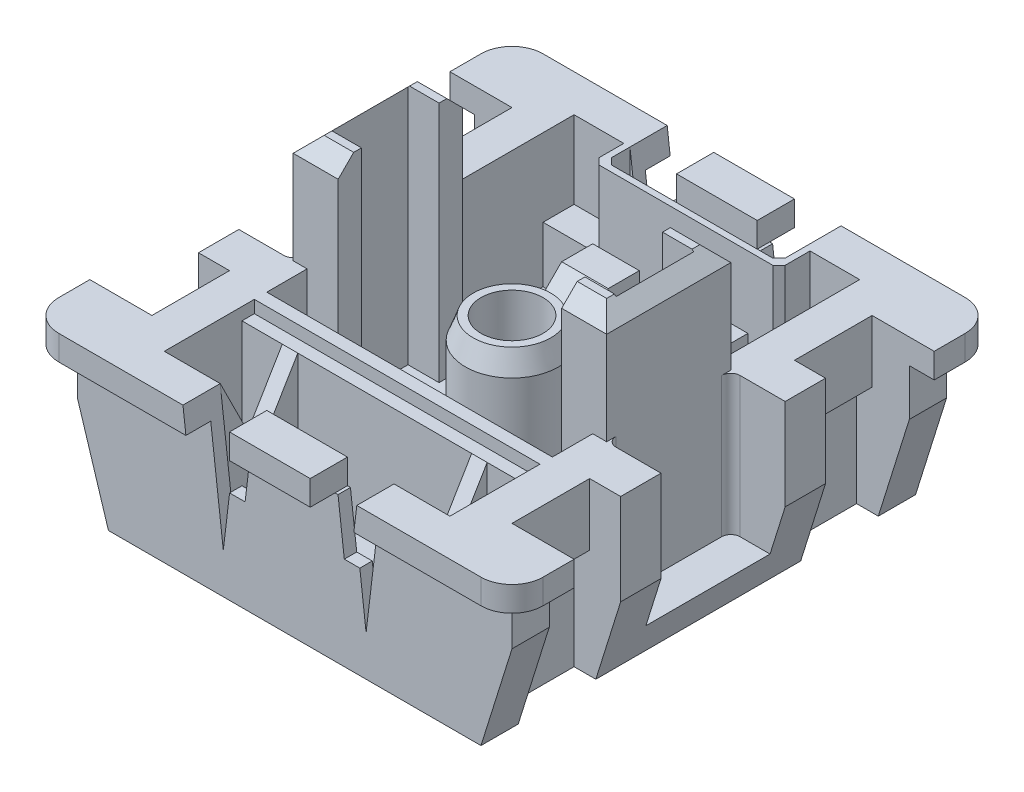
SolidWorks part; units mm, degrees
ref_plane "Front Plane" through (0, 0, 0) normal (0, 0, 1) x (1, 0, 0)
ref_plane "Top Plane" through (0, 0, 0) normal (0, 1, 0) x (1, 0, 0)
ref_plane "Right Plane" through (0, 0, 0) normal (1, 0, 0) x (0, 0, -1)
sketch "Sketch2" plane through (0, 0, 0) normal (0, 1, 0) x (1, 0, 0)
  line L1 (-7.8, 7.8) -> (7.8, 7.8)
  line L2 (-7.8, 7.8) -> (-7.8, -7.8)
  line L3 (-7.8, -7.8) -> (7.8, -7.8)
  line L4 (7.8, 7.8) -> (7.8, -7.8)
  line L5 (-7.8, 7.8) -> (7.8, -7.8) construction
  line L6 (-7.8, -7.8) -> (7.8, 7.8) construction
  point P0 (0, 0)
  dimension "D1" = 15.6
  dimension "D2" = 15.6
extrude "Boss-Extrude1" add sketch "Sketch2" along normal blind 5.5
sketch "Sketch3" plane through (0, 0, 0) normal (0, -1, 0) x (1, 0, 0)
  line L1 (-7.8, 7.8) -> (7.8, 7.8)
  line L2 (-7.8, 7.8) -> (-7.8, -7.8)
  line L3 (-7.8, -7.8) -> (7.8, -7.8)
  line L4 (7.8, 7.8) -> (7.8, -7.8)
  line L5 (-7.8, 7.8) -> (7.8, -7.8) construction
  line L6 (-7.8, -7.8) -> (7.8, 7.8) construction
  line L7 (-7, 7) -> (7, 7)
  line L8 (-7, 7) -> (-7, -7)
  line L9 (-7, -7) -> (7, -7)
  line L10 (7, 7) -> (7, -7)
  line L11 (-7, 7) -> (7, -7) construction
  line L12 (-7, -7) -> (7, 7) construction
  point P0 (0, 0)
  point P7 (0, 0)
  dimension "D1" = 14
extrude "Cut-Extrude1" cut sketch "Sketch3" against normal blind 4.7
sketch "Sketch4" plane through (0, 0, -7) normal (0, 0, -1) x (-1, 0, 0)
  line L0 (-7, 0) -> (-6, 0)
  line L1 (7, 0) -> (-7, 0) construction
  line L2 (-7, 0) -> (-7, 3.2)
  line L3 (-7, 4.7) -> (-7, 0) construction
  line L4 (-7, 3.2) -> (-6, 0)
  line L5 (7, 0) -> (7, 3.2)
  line L6 (7, 4.7) -> (7, 0) construction
  line L7 (7, 0) -> (6, 0)
  line L8 (6, 0) -> (7, 3.2)
  dimension "D1" = 3.2
  dimension "D2" = 1
  dimension "D3" = 1
extrude "Cut-Extrude2" cut sketch "Sketch4" against normal through all
sketch "Sketch5" plane through (0, 5.5, 0) normal (0, 1, 0) x (1, 0, 0)
  line L8 (-7.8, 7.8) -> (-7.8, -7.8) construction
  line L9 (-5.8, 5.8) -> (-7.8, 5.8)
  line L10 (-5.8, 5.8) -> (-5.8, 3.3)
  line L11 (-5.8, 3.3) -> (-7.8, 3.3)
  line L12 (5.8, -5.8) -> (5.8, 5.8)
  line L13 (5.8, 5.8) -> (-5.8, 5.8)
  line L14 (-5.8, 5.8) -> (-5.8, -5.8)
  line L15 (-5.8, -5.8) -> (5.8, -5.8)
  line L16 (5.8, -5.8) -> (5.8, 5.8)
  line L17 (5.8, 5.8) -> (-5.8, 5.8)
  line L18 (-5.8, 5.8) -> (-5.8, -5.8)
  line L19 (-5.8, -5.8) -> (5.8, -5.8)
  line L20 (-7.8, 5.8) -> (-7.8, 3.3)
  line L21 (7.8, -7.8) -> (7.8, 7.8) construction
  line L22 (-5.8, -5.8) -> (-7.8, -5.8)
  line L23 (-5.8, -5.8) -> (-5.8, -3.3)
  line L24 (-5.8, -3.3) -> (-7.8, -3.3)
  line L25 (-7.8, -5.8) -> (-7.8, -3.3)
  line L26 (5.8, 5.8) -> (7.8, 5.8)
  line L27 (5.8, 5.8) -> (5.8, 3.3)
  line L28 (5.8, 3.3) -> (7.8, 3.3)
  line L29 (7.8, 5.8) -> (7.8, 3.3)
  line L30 (-6.8, 3.3) -> (-6.8, -3.3)
  line L31 (5.8, -5.8) -> (7.8, -5.8)
  line L32 (5.8, -5.8) -> (5.8, -3.3)
  line L33 (5.8, -3.3) -> (7.8, -3.3)
  line L34 (7.8, -5.8) -> (7.8, -3.3)
  line L35 (6.8, 3.3) -> (6.8, -3.3)
  line L36 (-7.8, 3.3) -> (-7.8, -3.3)
  line L37 (7.8, 3.3) -> (7.8, -3.3)
  line M7 (7.8, -7.8) -> (7.8, 7.8)
  line M9 (-7.8, 7.8) -> (-7.8, -7.8)
  dimension "D2" = 2.5
  dimension "D3" = 2.5
  dimension "D1" = 2
extrude "Cut-Extrude3" cut sketch "Sketch5" against normal through all contours L11 L10 L9 M9 | L16 L28 L26 M7 | L18 L24 L22 M9 | L33 L16 L31 M7 | L30 L11 L24 M9 | L28 L35 L33 M7 region at (-6.8, 5.5, -4.55) region at (6.8, 5.5, -4.55) region at (-7.3, 5.5, 0) region at (-6.8, 5.5, 4.55) region at (6.8, 5.5, 4.55) region at (7.3, 5.5, 0)
sketch "Sketch6" plane through (0, 5.5, 0) normal (0, 1, 0) x (1, 0, 0)
  line L0 (-6.8, 3.3) -> (-6.8, -3.3) construction
  line L1 (-6.8, 2) -> (-5.05, 2)
  line L2 (-6.8, 2) -> (-6.8, -2)
  line L3 (-6.8, -2) -> (-5.05, -2)
  line L4 (-5.05, 2) -> (-5.05, -2)
  line L5 (-5.8, -3.3) -> (-6.8, -3.3) construction
  line L6 (6.8, 3.3) -> (6.8, -3.3) construction
  line L7 (6.8, 2) -> (5.05, 2)
  line L8 (6.8, 2) -> (6.8, -2)
  line L9 (6.8, -2) -> (5.05, -2)
  line L10 (5.05, 2) -> (5.05, -2)
  dimension "D1" = 1.75
  dimension "D2" = 1.3
  dimension "D3" = 1.3
  dimension "D4" = 1.75
  dimension "D5" = 4
extrude "Cut-Extrude4" cut sketch "Sketch6" against normal blind 4.5
sketch "Sketch7" plane through (0, 5.5, 0) normal (0, 1, 0) x (1, 0, 0)
  line L0 (7.8, 7.8) -> (-7.8, 7.8) construction
  line L1 (-5.8, 7.8) -> (-4.6, 7.8)
  line L2 (-5.8, 7.8) -> (-5.8, 6.6)
  line L3 (-5.8, 6.6) -> (-4.6, 6.6)
  line L4 (-4.6, 7.8) -> (-4.6, 6.6)
  line L5 (-7.8, -7.8) -> (7.8, -7.8) construction
  line L6 (5.8, -7.8) -> (4.6, -7.8)
  line L7 (5.8, -7.8) -> (5.8, -6.6)
  line L8 (5.8, -6.6) -> (4.6, -6.6)
  line L9 (4.6, -7.8) -> (4.6, -6.6)
  line L11 (-4.6, 6.6) -> (4.6, 6.6)
  line L12 (-4.6, 6.6) -> (-4.6, -6.6)
  line L13 (-4.6, -6.6) -> (4.6, -6.6)
  line L14 (4.6, 6.6) -> (4.6, -6.6)
  dimension "D1" = 1.2
  dimension "D2" = 1.2
  dimension "D3" = 2
  dimension "D4" = 2
  dimension "D5" = 1.2
  dimension "D6" = 1.2
extrude "Cut-Extrude5" cut sketch "Sketch7" against normal blind 4.3 contours L14 L11 L12 L13 region at (0, 5.5, 0)
sketch "Sketch8" plane through (0, 1.2, 0) normal (0, 1, 0) x (1, 0, 0)
  line L0 (4.6, 6.6) -> (4.6, -6.6) construction
  line L1 (4.6, -4.1) -> (-4.6, -4.1)
  line L2 (4.6, -4.1) -> (4.6, -3.3)
  line L3 (4.6, -3.3) -> (-4.6, -3.3)
  line L4 (-4.6, -4.1) -> (-4.6, -3.3)
  line L5 (-4.6, 6.6) -> (-4.6, -6.6) construction
  line L6 (-4.6, -6.6) -> (4.6, -6.6) construction
  dimension "D1" = 0.8
  dimension "D2" = 2.5
extrude "Boss-Extrude2" add sketch "Sketch8" along normal blind 4.3
sketch "Sketch9" plane through (0, 5.5, 0) normal (0, 1, 0) x (1, 0, 0)
  line L1 (4.6, -4.1) -> (-4.6, -4.1)
  line L2 (4.6, -4.1) -> (4.6, -3.7)
  line L3 (4.6, -3.7) -> (-4.6, -3.7)
  line L4 (-4.6, -4.1) -> (-4.6, -3.7)
  dimension "D1" = 0.4
extrude "Cut-Extrude6" cut sketch "Sketch9" against normal blind 0.4
sketch "Sketch10" plane through (0, 0, 7.8) normal (0, 0, 1) x (1, 0, 0)
  line L0 (7.8, 4.7) -> (-7.8, 4.7) construction
  line L1 (-7.8, 5.5) -> (-2.8, 5.5)
  line L2 (-7.8, 5.5) -> (-7.8, 4.7)
  line L3 (-7.8, 4.7) -> (-2.8, 4.7)
  line L4 (-2.8, 5.5) -> (-2.8, 4.7)
  line L5 (7, 4.7) -> (-7, 4.7) construction
  line L6 (7.8, 5.5) -> (2.8, 5.5)
  line L7 (7.8, 5.5) -> (7.8, 4.7)
  line L8 (7.8, 4.7) -> (2.8, 4.7)
  line L9 (2.8, 5.5) -> (2.8, 4.7)
  line L10 (-2.8, 5.5) -> (-1.3, 5.5)
  line L11 (-2.8, 5.5) -> (-2.8, 4.7)
  line L12 (-2.8, 4.7) -> (-1.3, 4.7)
  line L13 (-1.3, 5.5) -> (-1.3, 4.7)
  line L14 (-2.8, 1.3) -> (-2.3, 1.3)
  line L15 (2.8, 5.5) -> (1.3, 5.5)
  line L16 (2.8, 5.5) -> (2.8, 4.7)
  line L17 (2.8, 4.7) -> (1.3, 4.7)
  line L18 (1.3, 5.5) -> (1.3, 4.7)
  line L19 (-2.8, 4.7) -> (2.8, 4.7)
  line L20 (-2.8, 4.7) -> (-2.8, 1.3)
  line L21 (-2.8, 1.3) -> (2.8, 1.3)
  line L22 (2.8, 4.7) -> (2.8, 1.3)
  line L23 (2.8, 1.3) -> (2.3, 1.3)
  line L24 (-2.8, 5.5) -> (-2.3, 1.3)
  line L25 (2.8, 5.5) -> (2.3, 1.3)
  line L26 (-2.8, 5.5) -> (-1.8, 5.5)
  line L27 (2.8, 5.5) -> (1.8, 5.5)
  line L28 (6, 0) -> (-6, 0) construction
  line L29 (-2.8, 0) -> (2.8, 0)
  line L30 (-2.8, 0) -> (-2.8, 3)
  line L31 (-2.8, 3) -> (2.8, 3)
  line L32 (2.8, 0) -> (2.8, 3)
  line L33 (-2.3, 1.3) -> (-1.8, 1.3)
  line L34 (-2.3, 1.3) -> (-2.0976, 3)
  line L35 (2.3, 1.3) -> (2.0976, 3)
  line L36 (2.3, 1.3) -> (1.8, 1.3)
  line L37 (1.8, 1.3) -> (1.3, 5.5)
  line L38 (1.3, 5.5) -> (1.5976, 3)
  line L39 (1.5976, 3) -> (2.0976, 3)
  line L40 (-1.3, 5.5) -> (-1.8, 1.3)
  line L41 (-1.3, 5.5) -> (-1.5976, 3)
  line L42 (-1.5976, 3) -> (-2.0976, 3)
  line M23 (-7.8, 4.7) -> (7.8, 4.7)
  line M25 (7.8, 5.5) -> (-7.8, 5.5)
  dimension "D1" = 5
  dimension "D2" = 5
  dimension "D3" = 1.5
  dimension "D4" = 1.5
  dimension "D5" = 3.4
  dimension "D6" = 0.5
  dimension "D7" = 0.5
  dimension "D8" = 1
  dimension "D9" = 1
extrude "Cut-Extrude7" cut sketch "Sketch10" against normal blind 1.2 contours L40 L10 L24 L19 M25 | L13 L40 M23 | L40 L19 L24 L31 | L24 L34 L31 | L35 L25 L31 | L37 L31 L25 L19 | L37 L19 L25 L15 M25 | L37 L18 M23 region at (-2.05, 5.109, 7.8) region at (-2.05, 3.9018, 7.8) region at (-1.3317, 4.9667, 7.8) region at (-2.3, 2.4333, 7.8) region at (1.3317, 4.9667, 7.8) region at (2.05, 5.109, 7.8) region at (2.05, 3.9018, 7.8) region at (2.3, 2.4333, 7.8)
sketch "Sketch11" plane through (0, 1.2, 0) normal (0, 1, 0) x (1, 0, 0)
  line L0 (-4.6, -4.1) -> (4.6, -4.1) construction
  line L1 (-2.8, -6.6) -> (-3.3, -6.6)
  line L2 (-2.8, -6.6) -> (-2.8, -4.1)
  line L3 (-2.8, -4.1) -> (-3.3, -4.1)
  line L4 (-3.3, -6.6) -> (-3.3, -4.1)
  line L5 (-4.6, -4.1) -> (4.6, -4.1) construction
  line L6 (2.8, -6.6) -> (3.3, -6.6)
  line L7 (2.8, -6.6) -> (2.8, -4.1)
  line L8 (2.8, -4.1) -> (3.3, -4.1)
  line L9 (3.3, -6.6) -> (3.3, -4.1)
  dimension "D1" = 0.5
  dimension "D2" = 0.5
extrude "Boss-Extrude3" add sketch "Sketch11" along normal blind 4.3
sketch "Sketch12" plane through (3.3, 0, 0) normal (1, 0, 0) x (0, 0, -1)
  line L0 (-4.1, 5.1) -> (-5.35, 3)
  line L3 (-5.35, 3) -> (-6.6, 5.5)
  line L4 (-6.6, 5.5) -> (-4.1, 5.5)
  line L5 (-4.1, 5.5) -> (-4.1, 5.1)
extrude "Cut-Extrude8" cut sketch "Sketch12" against normal blind 6.6
fillet "Fillet2" radius 0.3 4 edges at (-5.05, 3.25, -2) (-5.05, 3.25, 2) (5.05, 3.25, -2) (5.05, 3.25, 2)
fillet "Fillet3" radius 1 4 edges at (7.8, 5.1, -7.8) (7.8, 5.1, 7.8) (-7.8, 5.1, -7.8) (-7.8, 5.1, 7.8)
sketch "Sketch13" plane through (0, 1.2, 0) normal (0, 1, 0) x (1, 0, 0)
  line L0 (0, 0) -> (4.6, 0)
  line L1 (4.6, 6.6) -> (4.6, -3.3) construction
  line L2 (4.6, 0) -> (4.6, -1.25)
  line L3 (4.6, -1.25) -> (3.6, -1.25)
  line L4 (3.6, -1.25) -> (3.6, -2)
  line L5 (3.6, -2) -> (4.6, -2)
  line L6 (4.6, -2) -> (4.6, -1.25)
  line L7 (4.6, 0) -> (4.6, 2)
  line L8 (4.6, 6.6) -> (4.6, -3.3) construction
  line L9 (-4.6, 6.6) -> (-4.6, -3.3) construction
  line L10 (4.6, 2) -> (3.6, 2)
  line L11 (4.6, 2) -> (4.6, 1.25)
  line L12 (4.6, 1.25) -> (3.6, 1.25)
  line L13 (3.6, 2) -> (3.6, 1.25)
  line L14 (-4.6, -2) -> (-3.6, -2)
  line L15 (-4.6, -2) -> (-4.6, -1.25)
  line L16 (-4.6, -1.25) -> (-3.6, -1.25)
  line L17 (-3.6, -2) -> (-3.6, -1.25)
  line L18 (-4.6, 6.6) -> (-4.6, -3.3) construction
  line L19 (-4.6, 2) -> (-3.6, 2)
  line L20 (-4.6, 2) -> (-4.6, 1.25)
  line L21 (-4.6, 1.25) -> (-3.6, 1.25)
  line L22 (-3.6, 2) -> (-3.6, 1.25)
  circle A0 centre (0, 0) radius 1
  circle A1 centre (0, 0) radius 1.5
  line M10 (-4.6, 6.6) -> (-4.6, -3.3)
  dimension "D8" = 2
  dimension "D9" = 3
  dimension "D1" = 1.25
  dimension "D2" = 1
  dimension "D3" = 0.75
  dimension "D4" = 2
  dimension "D5" = 0.75
  dimension "D6" = 1
  dimension "D7" = 1
extrude "Boss-Extrude4" add sketch "Sketch13" along normal blind 4.3 contours A1 A0 | L10 L13 L12 L7 | L22 L19 L21 M10 | L14 L17 L16 M10 | L3 L4 L5 L6 region at (-1.4576, 1.2, 0) region at (4.1, 1.2, -1.625) region at (-4.1, 1.2, 1.625) region at (-4.1, 1.2, -1.625)
sketch "Sketch14" plane through (0, 5.5, 0) normal (0, 1, 0) x (1, 0, 0)
  line L0 (-3.6, 2) -> (-5.05, 2)
  line L1 (-5.05, 2) -> (-5.05, -2)
  line L2 (-5.05, -2) -> (-3.6, -2)
  line L3 (-3.6, -2) -> (-3.6, -1.25)
  line L4 (-3.6, -1.25) -> (-4.6, -1.25)
  line L5 (-4.6, -1.25) -> (-4.6, 1.25)
  line L6 (-4.6, 1.25) -> (-3.6, 1.25)
  line L7 (-3.6, 1.25) -> (-3.6, 2)
  line L8 (-5.05, 2) -> (-3.6, 2)
  line L9 (3.6, 2) -> (5.05, 2)
  line L10 (5.05, 2) -> (5.05, -2)
  line L11 (5.05, -2) -> (3.6, -2)
  line L12 (3.6, -2) -> (3.6, -1.25)
  line L13 (3.6, -1.25) -> (4.6, -1.25)
  line L14 (4.6, -1.25) -> (4.6, 1.25)
  line L15 (4.6, 1.25) -> (3.6, 1.25)
  line L16 (3.6, 1.25) -> (3.6, 2)
extrude "Boss-Extrude5" add sketch "Sketch14" along normal blind 3.5 contours L6 L7 L0 L1 L2 L3 L4 L5 | L16 L15 L14 L13 L12 L11 L10 L9 region at (-3.6425, 5.5, -1.625) region at (4.325, 5.5, -1.9575)
chamfer "Chamfer3" distance 0.5 angle 45 6 edges at (4.325, 9, 2) (5.05, 9, 0) (4.325, 9, -2) (-4.325, 9, 2) (-4.325, 9, -2) (-5.05, 9, 0)
chamfer "Chamfer4" distance 0.25 angle 70 1 edges at (0, 5.5, 1.5) first distance on face at (0, 5.5, 1.5)
sketch "Sketch16" plane through (0, 1.2, 0) normal (0, 1, 0) x (1, 0, 0)
  line L0 (-3.6, 2) -> (-3.6, 1.25) construction
  line L2 (-2.5, 1.6) -> (-2.5, 5.1)
  line L4 (-2.5, 1.6) -> (-2.5, 5.1)
  line L5 (-2.5, 5.1) -> (2.5, 5.1)
  line L6 (2.5, 5.1) -> (2.5, 1.6)
  line L7 (2.5, 1.6) -> (1.9209, 1.6)
  line L8 (-1.9209, 1.6) -> (-2.5, 1.6)
  line L9 (-4.6, 6.6) -> (4.6, 6.6) construction
  line L10 (2.5, 5.1) -> (-2.5, 5.1)
  arc A0 (1.9209, 1.6) -> (-1.9209, 1.6) centre (0, 0) ccw
  dimension "D5" = 2.5
  dimension "D1" = 3.5
  dimension "D2" = 0
  dimension "D3" = 1.1
  dimension "D4" = 5
  dimension "D6" = 1.5
extrude "Boss-Extrude6" add sketch "Sketch16" along normal blind 2.5 contours A0 L7 L6 L5 L2 L8 region at (0, 1.2, -3.5703)
sketch "Sketch17" plane through (2.5, 0, 0) normal (1, 0, 0) x (0, 0, -1)
  line L1 (5.1, 3.7) -> (1.6, 3.7) construction
  line L2 (1.6, 3.7) -> (1.6, 3.2)
  line L3 (1.6, 3.7) -> (1.6, 1.2) construction
  line L4 (1.6, 3.2) -> (3.6, 3.2)
  line L5 (1.6, 3.7) -> (4.1, 3.7)
  line L6 (4.1, 3.7) -> (3.6, 3.2)
  dimension "D2" = 0.5
  dimension "D3" = 2
extrude "Cut-Extrude9" cut sketch "Sketch17" against normal blind 5
sketch "Sketch18" plane through (-2.5, 0, 0) normal (-1, 0, 0) x (0, 0, 1)
  line L0 (-3.6, 3.2) -> (-3.1, 3.2)
  line L1 (-1.6, 3.2) -> (-3.6, 3.2) construction
  line L2 (-3.1, 3.2) -> (-3.1, 2.7)
  line L3 (-3.6, 3.2) -> (-3.1, 2.7)
  dimension "D1" = 0.5
  dimension "D2" = 0.5
extrude "Cut-Extrude10" cut sketch "Sketch18" against normal blind 4.5
sketch "Sketch19" plane through (0, 3.2, 0) normal (0, 1, 0) x (1, 0, 0)
  line L1 (-2.5, 3.1) -> (2, 3.1)
  line L2 (-2.5, 3.1) -> (-2.5, 2.5)
  line L3 (-2.5, 2.5) -> (2, 2.5)
  line L4 (2, 3.1) -> (2, 2.5)
  line L5 (0, 2.5) -> (1, 2.5)
  line L6 (0, 2.5) -> (0, 2.2913)
  line L7 (0, 2.2913) -> (1, 2.2913)
  line L8 (1, 2.5) -> (1, 2.2913)
  line L9 (0, 2.5) -> (-1, 2.5)
  line L10 (0, 2.5) -> (0, 2.2913)
  line L11 (0, 2.2913) -> (-1, 2.2913)
  line L12 (-1, 2.5) -> (-1, 2.2913)
  arc A0 (1.9209, 1.6) -> (-1.9209, 1.6) centre (0, 0) ccw construction
  arc A1 (1.9209, 1.6) -> (-1.9209, 1.6) centre (0, 0) ccw construction
  line M2 (2, 3.1) -> (-2.5, 3.1)
  line M3 (-2.5, 3.1) -> (-2.5, 1.6)
  arc M5 (-1.9209, 1.6) -> (1.9209, 1.6) centre (0, 0) cw
  dimension "D1" = 1
  dimension "D2" = 1
  dimension "D3" = 0.6
extrude "Cut-Extrude15" cut sketch "Sketch19" against normal blind 2 contours L3 L12 M5 | L8 L3 M5 | L4 L3 M2 M3 region at (-0.25, 3.2, -2.8) region at (-0.7521, 3.2, -2.4379) region at (0.7521, 3.2, -2.4379)
sketch "Sketch20" plane through (0, 3.7, 0) normal (0, 1, 0) x (1, 0, 0)
  line L0 (-2.5, 5.1) -> (2.5, 5.1) construction
  line L1 (-1, 5.1) -> (1, 5.1)
  line L2 (-1, 5.1) -> (-1, 3.1)
  line L3 (-1, 3.1) -> (1, 3.1)
  line L4 (1, 5.1) -> (1, 3.1)
  line L5 (2, 3.1) -> (-2.5, 3.1) construction
  line L6 (-2.5, 4.1) -> (-2.5, 5.1) construction
  line L8 (2.5, 5.1) -> (2.5, 4.1) construction
  dimension "D1" = 1.5
  dimension "D2" = 1.5
extrude "Cut-Extrude16" cut sketch "Sketch20" against normal blind 1
chamfer "Chamfer5" distance 0.5 1 edges at (0, 2.7, -3.1)
sketch "Sketch21" plane through (0, 1.2, 0) normal (0, 1, 0) x (1, 0, 0)
  line L0 (4.6, 6.6) -> (4.6, 2) construction
  line L1 (-4.6, 6.6) -> (4.6, 6.6)
  line L2 (-4.6, 6.6) -> (-4.6, 5.6)
  line L3 (-4.6, 5.6) -> (4.6, 5.6)
  line L4 (4.6, 6.6) -> (4.6, 5.6)
  dimension "D1" = 1
extrude "Boss-Extrude7" add sketch "Sketch21" along normal up to surface (4.3 mm away) up to face at (0, 5.5, -4.1141)
sketch "Sketch22" plane through (0, 0, -7.8) normal (0, 0, -1) x (-1, 0, 0)
  line L0 (-7.8, 5.5) -> (-2.8, 5.5)
  line L1 (-7.8, 5.5) -> (-7.8, 4.7)
  line L2 (-7.8, 4.7) -> (-2.8, 4.7)
  line L3 (-2.8, 5.5) -> (-2.8, 4.7)
  line L4 (7.8, 5.5) -> (2.8, 5.5)
  line L5 (7.8, 5.5) -> (7.8, 4.7)
  line L6 (7.8, 4.7) -> (2.8, 4.7)
  line L7 (2.8, 5.5) -> (2.8, 4.7)
  line L8 (-2.8, 5.5) -> (-1.3, 5.5)
  line L9 (-2.8, 4.7) -> (-2.8, 0)
  line L10 (2.8, 4.7) -> (2.8, 0)
  line L11 (-1.3, 5.5) -> (-1.3, 4.7)
  line L13 (2.8, 5.5) -> (1.3, 5.5)
  line L16 (1.3, 5.5) -> (1.3, 4.7)
  line L17 (-2.8, 4.7) -> (2.8, 4.7)
  line L19 (-2.8, 1.3) -> (2.8, 1.3)
  line L22 (-2.8, 5.5) -> (-2.3, 1.3)
  line L23 (2.8, 5.5) -> (2.3, 1.3)
  line L26 (-2.8, 0) -> (2.8, 0)
  line L28 (-2.8, 3) -> (2.8, 3)
  line L31 (-2.3, 1.3) -> (-2.0976, 3)
  line L32 (2.3, 1.3) -> (2.0976, 3)
  line L34 (1.8, 1.3) -> (1.3, 5.5)
  line L37 (-1.3, 5.5) -> (-1.8, 1.3)
  line L40 (-7.8, 4.7) -> (-7.8, 5.5) construction
  line M8 (6.8, 5.5) -> (-6.8, 5.5)
  line M10 (-6.8, 4.7) -> (6.8, 4.7)
  dimension "D1" = 1.5
  dimension "D2" = 1.5
  dimension "D5" = 0
  dimension "D6" = 0.8
  dimension "D7" = 15.6
  dimension "D8" = 5
  dimension "D9" = 0
extrude "Cut-Extrude17" cut sketch "Sketch22" against normal blind 1.2 contours L37 L8 L22 L17 M8 | L37 L17 L22 L28 | L22 L31 L28 | L32 L23 L28 | L34 L28 L23 L17 | L34 L17 L23 L13 M8 | L11 L37 M10 | L34 L16 M10 region at (2.05, 5.109, -7.8) region at (1.3317, 4.9667, -7.8) region at (2.05, 3.9018, -7.8) region at (-1.3317, 4.9667, -7.8) region at (-2.05, 5.109, -7.8) region at (2.3, 2.4333, -7.8) region at (-2.05, 3.9018, -7.8) region at (-2.3, 2.4333, -7.8)
sketch "Sketch23" plane through (0, 5.5, 0) normal (0, 1, 0) x (1, 0, 0)
  line L1 (2.8, 6.6) -> (-2.8, 6.6)
  line L2 (2.8, 6.6) -> (2.8, 5.8)
  line L3 (2.8, 5.8) -> (-2.8, 5.8)
  line L4 (-2.8, 6.6) -> (-2.8, 5.8)
  dimension "D1" = 0.8
  dimension "D2" = 5.6
extrude "Cut-Extrude18" cut sketch "Sketch23" against normal blind 4.2
chamfer "Chamfer7" distance 0.2 angle 45 2 edges at (2.8, 3.4, -5.8) (-2.8, 3.4, -5.8)
sketch "Sketch24" plane through (0, 5.5, 0) normal (0, 1, 0) x (1, 0, 0)
  line L1 (4.6, 5.6) -> (3, 5.6)
  line L2 (4.6, 5.6) -> (4.6, 6.6)
  line L3 (4.6, 6.6) -> (3, 6.6)
  line L4 (3, 5.6) -> (3, 6.6)
  line L5 (-4.6, 5.6) -> (-3, 5.6)
  line L6 (-4.6, 5.6) -> (-4.6, 6.6)
  line L7 (-4.6, 6.6) -> (-3, 6.6)
  line L8 (-3, 5.6) -> (-3, 6.6)
  dimension "D1" = 1.6
  dimension "D2" = 1
  dimension "D3" = 1.6
  dimension "D4" = 1
extrude "Cut-Extrude19" cut sketch "Sketch24" against normal blind 2.5
chamfer "Chamfer8" distance 0.2 angle 45 2 edges at (-3, 4.25, -5.6) (3, 4.25, -5.6)
sketch "Sketch25" plane through (0, 1.2, 0) normal (0, 1, 0) x (1, 0, 0)
  line L0 (-4.6, -3.7) -> (-4.6, -6.6) construction
  line L9 (-4.2, -5.6) -> (-3.7, -5.6)
  line L10 (-4.2, -5.6) -> (-4.2, -5.1)
  line L11 (-4.2, -5.1) -> (-3.7, -5.1)
  line L12 (-3.7, -5.6) -> (-3.7, -5.1)
  line L13 (-4.2, -5.6) -> (-3.7, -5.1) construction
  line L14 (-4.2, -5.1) -> (-3.7, -5.6) construction
  line L15 (3.7, -5.6) -> (4.2, -5.6)
  line L16 (3.7, -5.6) -> (3.7, -5.1)
  line L17 (3.7, -5.1) -> (4.2, -5.1)
  line L18 (4.2, -5.6) -> (4.2, -5.1)
  line L19 (3.7, -5.6) -> (4.2, -5.1) construction
  line L20 (3.7, -5.1) -> (4.2, -5.6) construction
  line L21 (-4.6, -6.6) -> (-3.3, -6.6) construction
  line L22 (3.3, -6.6) -> (4.6, -6.6) construction
  line L23 (4.6, -3.7) -> (4.6, -6.6) construction
  circle A0 centre (1.45, -5.35) radius 0.25
  circle A1 centre (-1.45, -5.35) radius 0.25
  point P0 (-3.95, -5.35)
  point P6 (3.95, -5.35)
  dimension "D1" = 0.65
  dimension "D2" = 1.25
  dimension "D3" = 0.5
  dimension "D4" = 0.5
  dimension "D5" = 1.25
  dimension "D6" = 0.65
  dimension "D7" = 0.5
  dimension "D8" = 0.5
extrude "Cut-Extrude20" cut sketch "Sketch25" against normal through all
sketch "Sketch26" plane through (0, 0, 0) normal (0, -1, 0) x (1, 0, 0)
  circle A0 centre (0, 0) radius 2
  dimension "D1" = 4
extrude "Boss-Extrude8" add sketch "Sketch26" along normal blind 3
chamfer "Chamfer9" distance 0.5 angle 45 1 edges at (0, -3, -2)
sketch "Sketch27" plane through (0, 1.2, 0) normal (0, 1, 0) x (1, 0, 0)
  circle A0 centre (0, 0) radius 1
  dimension "D1" = 2
extrude "Cut-Extrude21" cut sketch "Sketch27" against normal blind 2
sketch "Sketch28" plane through (0, 0, 0) normal (0, -1, 0) x (1, 0, 0)
  line L0 (2.7048, -7) -> (7, -7) construction
  line L1 (4.5, -7) -> (1.5, -7)
  line L2 (4.5, -7) -> (4.5, -2)
  line L3 (4.5, -2) -> (1.5, -2)
  line L4 (1.5, -7) -> (1.5, -2)
  line L5 (5.8, -3.3) -> (5.8, -5.8) construction
  line L6 (-6, -7) -> (6, -7) construction
  line L7 (-4.5, -7) -> (-1.5, -7)
  line L8 (-4.5, -7) -> (-4.5, -2.1913)
  line L9 (-4.5, -2.1913) -> (-1.5, -2.1913)
  line L10 (-1.5, -7) -> (-1.5, -2.1913)
  line L11 (-6, -5.8) -> (-6, -7) construction
  dimension "D1" = 3
  dimension "D2" = 1.3
  dimension "D3" = 5
  dimension "D4" = 3
  dimension "D5" = 4.8087
  dimension "D6" = 1.5
extrude "Boss-Extrude9" add sketch "Sketch28" along normal blind 0.2
chamfer "Chamfer10" distance 1 angle 45 2 edges at (-1.5, -0.1, -2.1913) (1.5, -0.1, -2)
sketch "Sketch29" plane through (0, 1.2, 0) normal (0, 1, 0) x (1, 0, 0)
  line L3 (-3, 3.1) -> (-4, 3.1)
  line L4 (-3, 3.1) -> (-3, 2.5)
  line L5 (-3, 2.5) -> (-4, 2.5)
  line L6 (-4, 3.1) -> (-4, 2.5)
  dimension "D1" = 3
  dimension "D2" = 1
  dimension "D3" = 2.5
  dimension "D4" = 0.6
extrude "Cut-Extrude22" cut sketch "Sketch29" against normal through all
sketch "Sketch31" plane through (0, 0, 0) normal (0, -1, 0) x (1, 0, 0)
  line L1 (-5.8, -5.8) -> (-5.3, -5.8)
  line L2 (-5.8, -5.8) -> (-5.8, -3.3)
  line L3 (-5.8, -3.3) -> (-5.3, -3.3)
  line L4 (-5.3, -5.8) -> (-5.3, -3.3)
  line L5 (5.8, 5.8) -> (5.3, 5.8)
  line L6 (5.8, 5.8) -> (5.8, 3.3)
  line L7 (5.8, 3.3) -> (5.3, 3.3)
  line L8 (5.3, 5.8) -> (5.3, 3.3)
  line L9 (5.8, -5.8) -> (5.3, -5.8)
  line L10 (5.8, -5.8) -> (5.8, -3.3)
  line L11 (5.8, -3.3) -> (5.3, -3.3)
  line L12 (5.3, -5.8) -> (5.3, -3.3)
  line L13 (-5.8, 5.8) -> (-5.3, 5.8)
  line L14 (-5.8, 5.8) -> (-5.8, 3.3)
  line L15 (-5.8, 3.3) -> (-5.3, 3.3)
  line L16 (-5.3, 5.8) -> (-5.3, 3.3)
  dimension "D1" = 0.5
  dimension "D2" = 2.5
  dimension "D3" = 0.5
  dimension "D4" = 2.5
extrude "Cut-Extrude25" cut sketch "Sketch31" against normal blind 4
sketch "Sketch32" plane through (0, 1.2, 0) normal (0, 1, 0) x (1, 0, 0)
  line L0 (-3, 3.1) -> (-4, 3.1) construction
  line L1 (3, 5.6) -> (2, 5.6)
  line L2 (3, 5.6) -> (3, 5.5)
  line L3 (3, 5.5) -> (2, 5.5)
  line L4 (2, 5.6) -> (2, 5.5)
  line L5 (-2.5, 5.1) -> (2.5, 5.1) construction
  point P8 (0, 5.1)
  dimension "D1" = 2.5
  dimension "D2" = 2
  dimension "D3" = 0.1
  dimension "D4" = 1
extrude "Cut-Extrude26" cut sketch "Sketch32" against normal through all
sketch "Sketch37" plane through (0, 4, 0) normal (0, -1, 0) x (1, 0, 0)
  line L1 (-5.3, -3.3) -> (-5.8, -3.3)
  line L2 (-5.3, -3.3) -> (-5.3, -5.8)
  line L3 (-5.3, -5.8) -> (-5.8, -5.8)
  line L4 (-5.8, -3.3) -> (-5.8, -5.8)
  line L5 (-5.3, 3.3) -> (-5.8, 3.3)
  line L6 (-5.3, 3.3) -> (-5.3, 5.8)
  line L7 (-5.3, 5.8) -> (-5.8, 5.8)
  line L8 (-5.8, 3.3) -> (-5.8, 5.8)
  line L9 (5.3, 3.3) -> (5.8, 3.3)
  line L10 (5.3, 3.3) -> (5.3, 5.8)
  line L11 (5.3, 5.8) -> (5.8, 5.8)
  line L12 (5.8, 3.3) -> (5.8, 5.8)
  line L13 (5.3, -3.3) -> (5.8, -3.3)
  line L14 (5.3, -3.3) -> (5.3, -5.8)
  line L15 (5.3, -5.8) -> (5.8, -5.8)
  line L16 (5.8, -3.3) -> (5.8, -5.8)
extrude "Boss-Extrude10" add sketch "Sketch37" along normal blind 0.5
